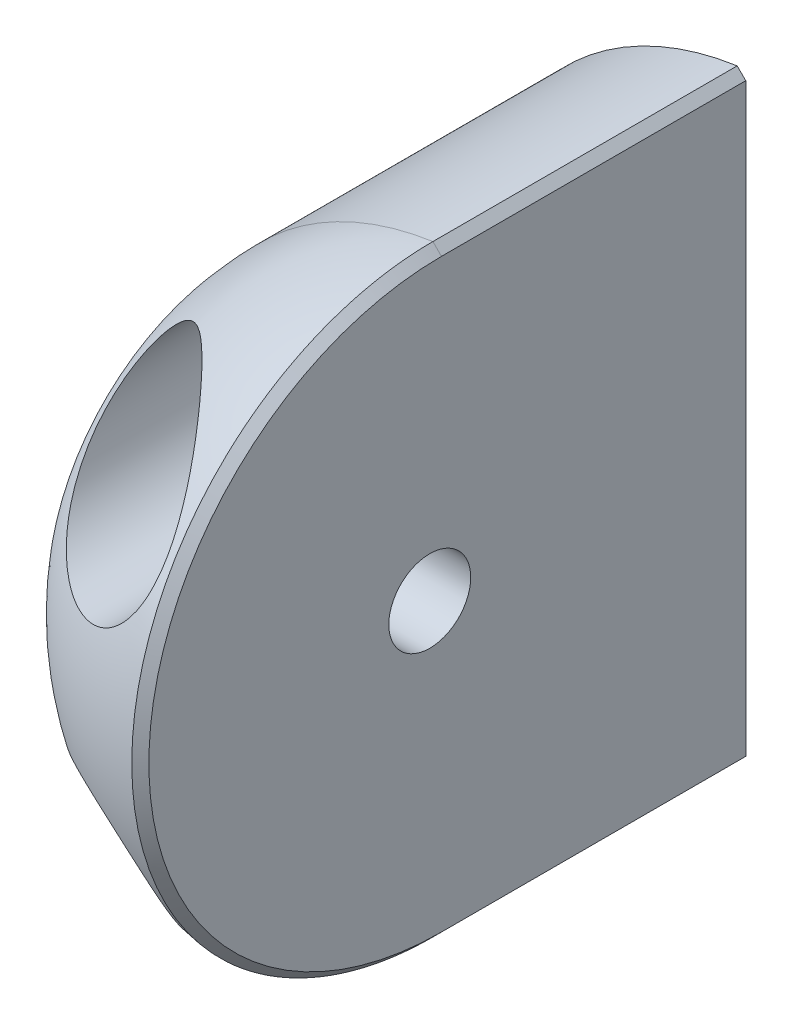
SolidWorks part; units mm, degrees
ref_plane "Plano frontal" through (0, 0, 0) normal (0, 0, 1) x (1, 0, 0)
ref_plane "Plano superior" through (0, 0, 0) normal (0, 1, 0) x (1, 0, 0)
ref_plane "Plano direito" through (0, 0, 0) normal (1, 0, 0) x (0, 0, -1)
sketch "Esboço1" plane through (0, 0, 0) normal (0, 0, 1) x (1, 0, 0)
  line L0 (0, 47.2571) -> (8.5, 47.2571)
  line L1 (0, 47.2571) -> (-8.5, 47.2571)
  line L2 (0, 23.9177) -> (8.5, 23.9177)
  line L3 (0, 23.9177) -> (-8.5, 23.9177)
  line L4 (0, 8.4) -> (0, 75) construction
  line L5 (0, 56.3545) -> (-16, 56.3545) construction
  line L6 (0, 56.3545) -> (16, 56.3545) construction
  line L7 (8.5, 47.2571) -> (8.5, 23.9177)
  line L8 (-8.5, 47.2571) -> (-8.5, 23.9177)
  line L20 (19.3117, 92) -> (-19.3117, 92)
  line L21 (-19.3117, 92) -> (-36.5, 70)
  line L22 (-36.5, 70) -> (-36.5, 0)
  line L23 (-36.5, 0) -> (-22.5, 0)
  line L24 (-22.5, 0) -> (-22.5, 8.4)
  line L25 (-22.5, 8.4) -> (22.5, 8.4)
  line L26 (22.5, 8.4) -> (22.5, 0)
  line L27 (22.5, 0) -> (36.5, 0)
  line L28 (36.5, 0) -> (36.5, 70)
  line L29 (36.5, 70) -> (19.3117, 92)
  circle A8 centre (29.2, 62) radius 2
  circle A9 centre (29.2, 49) radius 2
  circle A10 centre (29.2, 36) radius 2
  circle A11 centre (29.2, 23) radius 2
  circle A12 centre (-29.2, 23) radius 2
  circle A13 centre (0, 75) radius 2
  circle A14 centre (-7, 83.3) radius 2
  circle A15 centre (7, 83.3) radius 2
  circle A16 centre (-29.2, 36) radius 2
  circle A17 centre (-29.2, 49) radius 2
  circle A18 centre (-29.2, 62) radius 2
  circle A20 centre (-29.2, 10) radius 2
  circle A21 centre (29.2, 10) radius 2
  circle A26 centre (-16, 56.3545) radius 2.0867
  circle A27 centre (16, 56.3545) radius 2.0867
  point P31 (0, 23.9177)
  point P33 (0, 47.2571)
sketch "Esboço2" plane through (0, 0, 0) normal (0, 0, 1) x (1, 0, 0)
  line L0 (-29.2, 49) -> (-29.2, 62) construction
  line L1 (-29.2, 55.5) -> (-36.5, 55.5) construction
  line L2 (-36.5, 70) -> (-36.5, 0) construction
  line L3 (-29.2, 48.2) -> (-29.2, 62.8) construction
  line L4 (-23.5, 42.5) -> (-23.5, 68.5)
  arc A0 (-23.5, 68.5) -> (-23.5, 42.5) centre (-23.5, 55.5) ccw
revolve "Revolução1" add sketch "Esboço2" angle 90 about L4
sketch "Esboço3" plane through (0, 0, 0) normal (0, 0, 1) x (1, 0, 0)
  circle A2 centre (-29.2, 62) radius 2.5
  circle A3 centre (-29.2, 49) radius 2.5
extrude "Corte-extrusão1" cut sketch "Esboço3" along normal through all
sketch "Esboço7" plane through (0, 0, 0) normal (0, 0, -1) x (-1, 0, 0)
  line L1 (23.5, 68.5) -> (23.5, 42.5)
  line L2 (23.5, 68.5) -> (23.5, 42.5)
  arc A1 (23.5, 42.5) -> (23.5, 68.5) centre (23.5, 55.5) ccw
  arc A2 (23.5, 42.5) -> (23.5, 68.5) centre (23.5, 55.5) ccw
  circle A4 centre (29.2, 62) radius 2.5
  circle A5 centre (29.2, 49) radius 2.5
  dimension "D1" = 0
extrude "Ressalto-extrusão1" add sketch "Esboço7" along normal blind 13
sketch "Esboço4" plane through (0, 0, 0) normal (0, 0, 1) x (1, 0, 0)
  circle A2 centre (-29.2, 62) radius 3.5
  circle A3 centre (-29.2, 49) radius 3.5
extrude "Corte-extrusão3" cut sketch "Esboço4" along normal through all and the other way blind 6.5
sketch "Esboço6" plane through (-23.5, 0, 0) normal (1, 0, 0) x (0, 0, -1)
  line L0 (-13, 55.5) -> (-0.5, 55.5) construction
  arc A0 (0, 68.5) -> (0, 42.5) centre (0, 55.5) ccw construction
  circle A1 centre (-0.5, 55.5) radius 12.5 construction
  circle A2 centre (-0.5, 55.5) radius 1.75
extrude "Corte-extrusão4" cut sketch "Esboço6" against normal through all
sketch "Esboço8" plane through (-23.5, 0, 0) normal (1, 0, 0) x (0, 0, -1)
  circle A1 centre (-0.5, 55.5) radius 3.1
extrude "Corte-extrusão5" cut sketch "Esboço8" against normal blind 13 from offset 6.5 offset against normal yes
chamfer "Chanfro1" distance 2 angle 45 3 edges at (-23.5, 68.5, -6.5) (-23.5, 55.5, 13) (-23.5, 42.5, -6.5)
sketch "Esboço9" plane through (0, 0, -13) normal (0, 0, -1) x (-1, 0, 0)
  line L0 (36.5, 55.5) -> (33.5, 55.5) construction
  line L1 (33.5, 47.1934) -> (33.5, 63.8066)
  arc A0 (25.3655, 42.6345) -> (25.3655, 68.3655) centre (23.5, 55.5) ccw construction
  arc A1 (33.5, 47.1934) -> (33.5, 63.8066) centre (23.5, 55.5) ccw
extrude "Corte-extrusão6" cut sketch "Esboço9" against normal through all
sketch "Esboço10" plane through (0, 0, -13) normal (0, 0, -1) x (-1, 0, 0)
  line L0 (23.5, 55.5) -> (25, 55.5) construction
  line L1 (25, 68) -> (25, 43)
  line L4 (33.5, 47.1934) -> (33.5, 63.8066)
  line L5 (25.3655, 68.3655) -> (23.5, 66.5)
  line L6 (23.5, 66.5) -> (23.5, 44.5)
  line L7 (23.5, 44.5) -> (25.3655, 42.6345)
  line L9 (25, 68) -> (23.5, 66.5)
  line L10 (23.5, 66.5) -> (23.5, 44.5)
  line L11 (23.5, 44.5) -> (25, 43)
  arc A2 (33.5, 63.8066) -> (25.3655, 68.3655) centre (23.5, 55.5) ccw
  arc A3 (25.3655, 42.6345) -> (33.5, 47.1934) centre (23.5, 55.5) ccw
  dimension "D1" = 0
extrude "Corte-extrusão7" cut sketch "Esboço10" against normal through all
